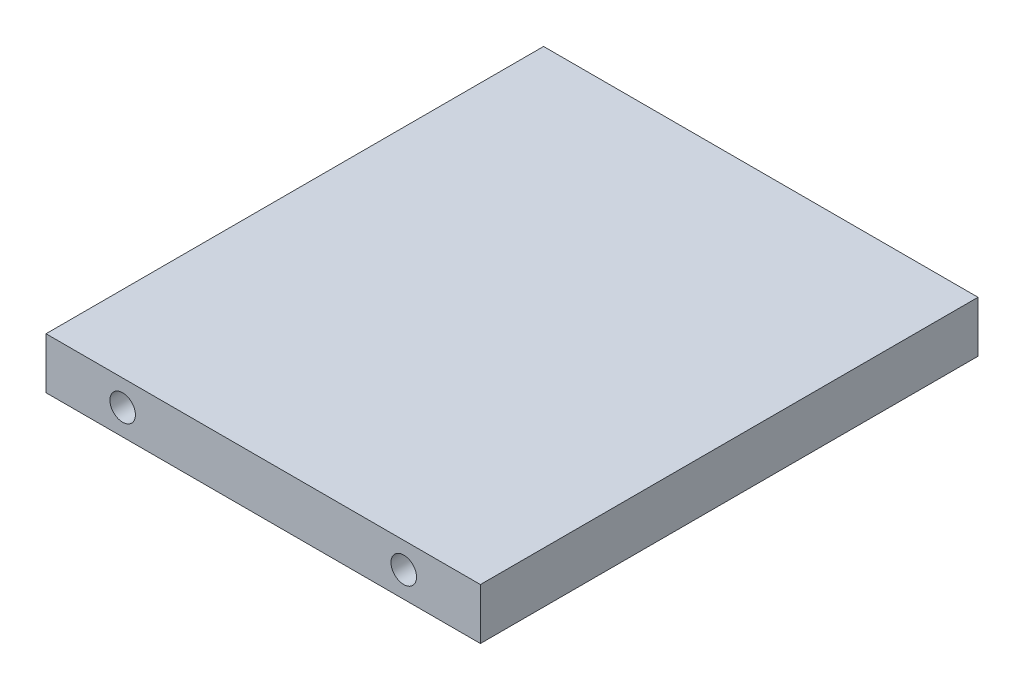
SolidWorks part; units mm, degrees
material "6061-T6 (SS)"
ref_plane "Front Plane" through (0, 0, 0) normal (0, 0, 1) x (1, 0, 0)
ref_plane "Top Plane" through (0, 0, 0) normal (0, 1, 0) x (1, 0, 0)
ref_plane "Right Plane" through (0, 0, 0) normal (1, 0, 0) x (0, 0, -1)
sketch "Sketch1" plane through (0, 0, 0) normal (0, 0, 1) x (1, 0, 0)
  line L1 (0, 0) -> (107.95, 0)
  line L2 (0, 0) -> (0, -12.7)
  line L3 (0, -12.7) -> (107.95, -12.7)
  line L4 (107.95, 0) -> (107.95, -12.7)
  line L5 (0, 0) -> (107.95, -12.7) construction
  line L6 (0, -12.7) -> (107.95, 0) construction
  point P5 (53.975, -6.35)
  dimension "D1" = 12.7
  dimension "D2" = 107.95
extrude "Boss-Extrude1" add sketch "Sketch1" along normal blind 123.65
sketch "Sketch2" plane through (0, 0, 123.65) normal (0, 0, 1) x (1, 0, 0)
  line L0 (0, -6.35) -> (107.95, -6.35) construction
  line L1 (0, 0) -> (0, -12.7) construction
  line L2 (107.95, -12.7) -> (107.95, 0) construction
  circle A0 centre (19.05, -6.35) radius 3.175
  circle A1 centre (88.9, -6.35) radius 3.175
  dimension "D1" = 6.35
  dimension "D2" = 6.35
  dimension "D3" = 19.05
  dimension "D4" = 19.05
extrude "Cut-Extrude1" cut sketch "Sketch2" against normal blind 25.4
ref_plane "Plane1" through (0, 0, 61.825) normal (0, 0, 1) x (1, 0, 0)
mirror "Mirror1" about plane through (0, 0, 61.825) normal (0, 0, 1) of "Cut-Extrude1"
